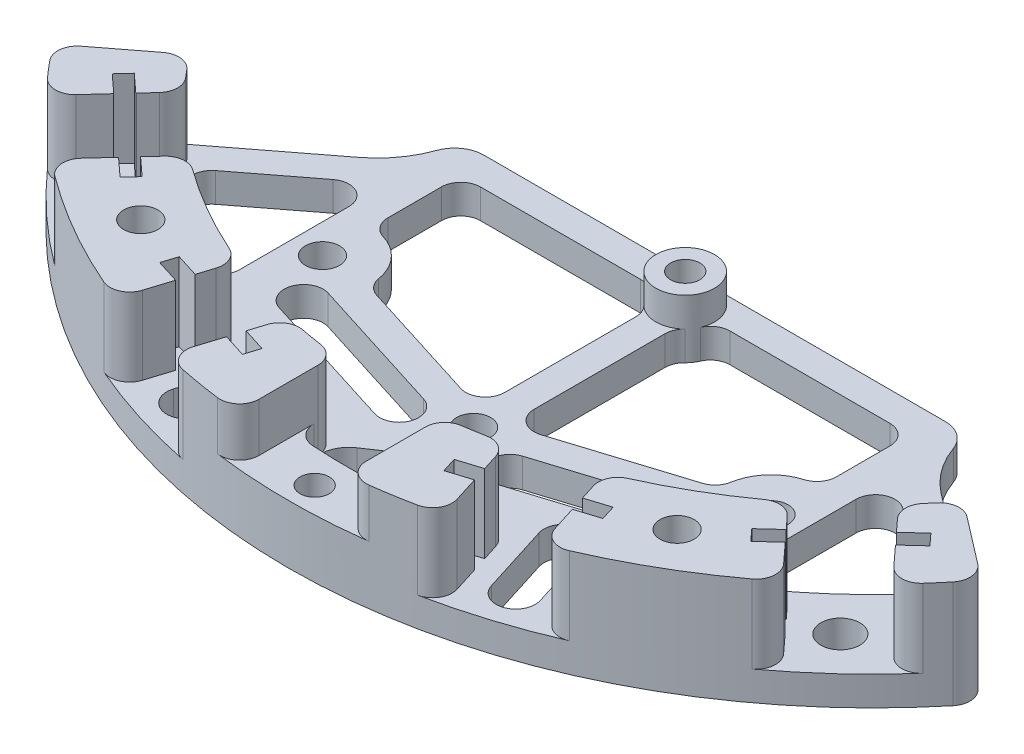
SolidWorks part; units mm, degrees
note: '?' marks a value the reader was unsure of.
ref_plane "Front Plane" through (0, 0, 0) normal (0, 0, 1) x (1, 0, 0)
ref_plane "Top Plane" through (0, 0, 0) normal (0, 1, 0) x (1, 0, 0)
ref_plane "Right Plane" through (0, 0, 0) normal (1, 0, 0) x (0, 0, -1)
sketch "Sketch1" plane through (0, 0, 0) normal (0, 1, 0) x (1, 0, 0)
  line L0 (-26, -16.3) -> (26, -16.3)
  line L3 (0, 0) -> (0, -80774.1077) construction
  line L5 (-47.6012, -36.5257) -> (-26, -19.9505)
  line L6 (-26, -19.9505) -> (-26, -16.3)
  line L7 (47.6012, -36.5257) -> (26, -19.9505)
  line L8 (26, -19.9505) -> (26, -16.3)
  arc A0 (-47.6012, -36.5257) -> (47.6012, -36.5257) centre (0, 0) ccw
  dimension "D1" = 60
  dimension "D2" = 105
  dimension "D4" = 52
  dimension "D5" = 16.3
extrude "Boss-Extrude1" add sketch "Sketch1" along normal blind 3
sketch "Sketch2" plane through (0, 3, 0) normal (0, 1, 0) x (1, 0, 0)
  line L0 (26, -16.3) -> (-26, -16.3) construction
  line L1 (0, 0) -> (0, -50000) construction
  circle A0 centre (-23, -33.5) radius 1.75
  circle A1 centre (23, -33.5) radius 1.75
  dimension "D1" = 3.5
  dimension "D2" = 17.2
  dimension "D3" = 46
extrude "Cut-Extrude1" cut sketch "Sketch2" against normal through all
sketch "Sketch3" plane through (0, 3, 0) normal (0, 1, 0) x (1, 0, 0)
  line L0 (-47.6012, -36.5257) -> (-39.6677, -30.4381)
  line L1 (-43.3943, -41.4359) -> (-40.0825, -37.8217)
  line L2 (-32.238, -50.6035) -> (-26.865, -42.1696)
  line L3 (-40.0825, -37.8217) -> (-41.9257, -36.1327)
  line L4 (-41.9257, -36.1327) -> (-40.8448, -34.953)
  line L5 (-40.8448, -34.953) -> (-39.0016, -36.642)
  line L6 (-39.0016, -36.642) -> (-36.6204, -34.0434)
  line L7 (-30.7221, -39.4481) -> (-33.1034, -42.0467)
  line L8 (-33.1034, -42.0467) -> (-31.2602, -43.7357)
  line L9 (-31.2602, -43.7357) -> (-32.3411, -44.9154)
  line L10 (-32.3411, -44.9154) -> (-34.1843, -43.2264)
  line L11 (-34.1843, -43.2264) -> (-37.4961, -46.8406)
  line L12 (-3.1979, -3.4899) -> (-31694.9476, -34588.9658) construction
  line L13 (-11.1484, -63.2498) -> (-34596.7728, 31628.636) construction
  line L14 (0, -2.3226) -> (0, -50002.3226) construction
  line L15 (-26, -19.9505) -> (-47.6012, -36.5257) construction
  arc A0 (-47.6012, -36.5257) -> (-43.3943, -41.4359) centre (0, 0) ccw
  arc A1 (-47.6012, -36.5257) -> (47.6012, -36.5257) centre (0, 0) ccw construction
  arc A2 (-39.6677, -30.4381) -> (-36.6204, -34.0434) centre (0, 0) ccw
  arc A3 (-30.7221, -39.4481) -> (-26.865, -42.1696) centre (0, 0) ccw
  arc A4 (-37.4961, -46.8406) -> (-32.238, -50.6035) centre (0, 0) ccw
  point P26 (-29.5515, -46.3865)
  point P27 (-43.6344, -33.4819)
  dimension "D1" = 20
  dimension "D2" = 10
  dimension "D3" = 1.6
  dimension "D4" = 13
  dimension "D5" = 8
extrude "Boss-Extrude2" add sketch "Sketch3" along normal blind 8
ref_axis "Axis1" through (0, -0.65, 0) along (0, 1, 0)?
pattern_circular "CirPattern1" count 2 every 25 about axis through (0, 0, 0) along (0, 1, 0) of "Boss-Extrude2"
sketch "Sketch5" plane through (0, 3, 0) normal (0, 1, 0) x (1, 0, 0)
  line L0 (-23.0874, -44.3505) -> (-27.7049, -53.2206) construction
  line L1 (-32.238, -50.6035) -> (-26.865, -42.1696)
  line L2 (-23.0874, -44.3505) -> (-27.7049, -53.2206)
  arc A0 (-26.865, -42.1696) -> (-23.0874, -44.3505) centre (0, 0) ccw
  arc A1 (-32.238, -50.6035) -> (-27.7049, -53.2206) centre (0, 0) ccw
extrude "Boss-Extrude3" add sketch "Sketch5" along normal up to surface (8 mm away) up to face at (-32.2866, 11, 44.1378)
sketch "Sketch19" plane through (0, 11, 0) normal (0, 1, 0) x (1, 0, 0)
  line L0 (0, 0) -> (-25000, -43301.2702) construction
  line L1 (-30.7221, -39.4481) -> (-33.1034, -42.0467) construction
  line L2 (-19.8619, -49.6917) -> (-18.802, -46.3302) construction
  circle A0 centre (-27.5, -47.6314) radius 1.75
  dimension "D1" = 3.5
  dimension "D2" = 55
extrude "Cut-Extrude11" cut sketch "Sketch19" against normal through all
mirror "Mirror1" about plane through (0, 0, 0) normal (1, 0, 0) of "Cut-Extrude11", "CirPattern1", "Boss-Extrude2", "Boss-Extrude3"
fillet "Fillet2" radius 10 2 edges at (26, 1.5, 19.9505) (-26, 1.5, 19.9505)
sketch "Sketch6" plane through (0, 3, 0) normal (0, 1, 0) x (1, 0, 0)
  line L1 (-7.0484, -53.538) -> (-7.8316, -59.4867)
  line L2 (7.0484, -53.538) -> (7.8316, -59.4867)
  line L3 (0, -1.1899) -> (0, -50001.1899) construction
  line L4 (26, -16.3) -> (-26, -16.3) construction
  arc A0 (-7.0484, -53.538) -> (7.0484, -53.538) centre (0, 0) ccw
  arc A1 (-7.8316, -59.4867) -> (7.8316, -59.4867) centre (0, 0) ccw
  arc A2 (-7.8316, -59.4867) -> (7.8316, -59.4867) centre (0, 0) ccw construction
  circle A3 centre (0, -19.3) radius 3
  dimension "D1" = 6
  dimension "D2" = 6
extrude "Boss-Extrude4" add sketch "Sketch6" along normal blind 3
sketch "Sketch12" plane through (0, 3, 0) normal (0, 1, 0) x (1, 0, 0)
  line L0 (0, 0) -> (0, -50000) construction
  line L1 (-5.5, -49.6966) -> (-5.5, -59.7474)
  line L2 (-7.8316, -59.4867) -> (-6.5263, -49.5722)
  arc A0 (-6.5263, -49.5722) -> (-5.5, -49.6966) centre (0, 0) ccw
  arc A1 (-7.8316, -59.4867) -> (-5.5, -59.7474) centre (0, 0) ccw
  dimension "D1" = 5.5
extrude "Boss-Extrude5" add sketch "Sketch12" along normal up to surface (8 mm away)
mirror "Mirror5" about plane through (0, 0, 0) normal (1, 0, 0) of "Boss-Extrude5"
sketch "Sketch7" plane through (0, 6, 0) normal (0, 1, 0) x (1, 0, 0)
  line L0 (0, 0) -> (0, -50000) construction
  circle A0 centre (0, -19.3) radius 1.5
  circle A1 centre (0, -57.3) radius 1.5
  dimension "D2" = 3
  dimension "D1" = 38
extrude "Cut-Extrude2" cut sketch "Sketch7" against normal through all
ref_plane "Plane1" through (0, 0, 0) normal (0.7373, 0, 0.6756) x (0.6756, 0, -0.7373)
ref_plane "Plane2" through (0, 0, 0) normal (-0.9537, 0, -0.3007) x (-0.3007, 0, 0.9537)
ref_plane "Plane3" through (0, 0, 0) normal (-0.9537, 0, 0.3007) x (0.3007, 0, 0.9537)
ref_plane "Plane4" through (0, 0, 0) normal (0.7373, 0, -0.6756) x (-0.6756, 0, -0.7373)
sketch "Sketch10" plane through (0, 0, 0) normal (0, -1, 0) x (1, 0, 0)
  line L0 (19.9851, 38.4432) -> (5.6793, 42.9538) construction
  line L1 (19.3837, 36.5358) -> (5.0779, 41.0464)
  line L2 (20.5865, 40.3507) -> (6.2807, 44.8613)
  line L3 (0, 0) -> (15035.29, 47685.8475) construction
  line L4 (17.8908, 35.958) -> (23.9049, 55.0323) construction
  line L5 (11.9835, 58.7911) -> (5.9693, 39.7168) construction
  line L6 (0, 0) -> (0, 50000) construction
  line L7 (5.9693, 39.7168) -> (17.8908, 35.958) construction
  arc A0 (19.3837, 36.5358) -> (20.5865, 40.3507) centre (19.9851, 38.4432) ccw
  arc A1 (6.2807, 44.8613) -> (5.0779, 41.0464) centre (5.6793, 42.9538) ccw
  point P3 (12.8322, 40.6985)
  dimension "D1" = 15
  dimension "D2" = 2
  dimension "D3" = 3
extrude "Cut-Extrude3" cut sketch "Sketch10" against normal up to next
mirror "Mirror2" about plane through (0, 0, 0) normal (1, 0, 0) of "Cut-Extrude3"
sketch "Sketch11" plane through (0, 3, 0) normal (0, 1, 0) x (1, 0, 0)
  line L0 (-23, -19.3) -> (-3, -19.3)
  line L1 (-1.5, -21.8981) -> (-1.5, -39.0289)
  line L2 (-1.5, -39.0289) -> (-18.0105, -33.8232)
  line L3 (-23, -19.3) -> (-23, -28.5)
  line L4 (-5.0779, -41.0464) -> (-19.3837, -36.5358) construction
  line L5 (0, 0) -> (0, -50000) construction
  line L6 (0, -16.3) -> (-26, -16.3) construction
  line L7 (-26, -23.7319) -> (-26, -42.7083)
  line L8 (-26, -23.7319) -> (-37.7699, -32.7633)
  line L9 (-29.8207, -22.8822) -> (-39.6677, -30.4381) construction
  line L10 (-0.5806, -0.6337) -> (-33780.091, -36864.5005) construction
  line L11 (0, 0) -> (-15035.29, -47685.8475) construction
  line L12 (-39.0016, -36.642) -> (-36.6204, -34.0434) construction
  line L13 (-30.7221, -39.4481) -> (-33.1034, -42.0467) construction
  line L14 (-19.8619, -49.6917) -> (-18.802, -46.3302) construction
  line L15 (-11.1722, -48.7358) -> (-12.2321, -52.0974) construction
  line L16 (-16.8917, -53.5737) -> (-14.6364, -46.4208) construction
  line L17 (-18.7992, -52.9723) -> (-16.5439, -45.8194)
  line L18 (-14.9843, -54.1751) -> (-12.729, -47.0222)
  line L19 (-20.5865, -40.3507) -> (-6.2807, -44.8613) construction
  arc A0 (-18.0105, -33.8232) -> (-23, -28.5) centre (-23, -33.5) ccw
  arc A1 (-3, -19.3) -> (-1.5, -21.8981) centre (0, -19.3) ccw
  arc A2 (-37.7699, -32.7633) -> (-26, -42.7083) centre (0, 0) ccw
  arc A3 (-39.6677, -30.4381) -> (-36.6204, -34.0434) centre (0, 0) ccw construction
  circle A4 centre (0, -19.3) radius 3 construction
  circle A5 centre (-37.1575, -40.5503) radius 2
  arc A6 (-18.7992, -52.9723) -> (-14.9843, -54.1751) centre (-16.8917, -53.5737) ccw
  arc A7 (-12.729, -47.0222) -> (-16.5439, -45.8194) centre (-14.6364, -46.4208) ccw
  point P44 (-15.7641, -49.9973)
  dimension "D5" = 5
  dimension "D6" = 3
  dimension "D8" = 4
  dimension "D1" = 3
  dimension "D2" = 3
  dimension "D3" = 3
  dimension "D4" = 23
  dimension "D7" = 3
  dimension "D9" = 4
  dimension "D10" = 7.5
  dimension "D11" = 55
extrude "Cut-Extrude4" cut sketch "Sketch11" against normal through all
fillet "Fillet3" radius 2 9 edges at (-1.5, 1.5, 39.0289) (-1.5, 1.5, 21.8981) (-3, 1.5, 19.3) (-18.0105, 1.5, 33.8232) (-23, 1.5, 28.5) (-23, 1.5, 19.3) (-37.7699, 1.5, 32.7633) (-26, 1.5, 42.7083) (-26, 1.5, 23.7319)
mirror "Mirror3" about plane through (0, 0, 0) normal (1, 0, 0) of "Fillet3", "Cut-Extrude4"
sketch "Sketch17" plane through (0, 3, 0) normal (0, 1, 0) x (1, 0, 0)
  line L0 (5.5, -53.7192) -> (5.5, -49.6966)
  line L1 (5.5, -49.6966) -> (0, -46)
  line L2 (0, -46) -> (-5.5, -49.6966)
  line L3 (-5.5, -49.6966) -> (-5.5, -53.7192)
  line L4 (0, 0) -> (0, -50000) construction
  arc A0 (-5.5, -53.7192) -> (5.5, -53.7192) centre (0, 0) ccw
  dimension "D1" = 46
extrude "Cut-Extrude10" cut sketch "Sketch17" against normal through all
fillet "Fillet1" radius 2 29 edges at (-47.6012, 5.5, 36.5257) (47.6012, 5.5, 36.5257) (43.3943, 7, 41.4359) (39.6677, 7, 30.4381) (36.6204, 7, 34.0434) (37.4961, 7, 46.8406) (30.7221, 7, 39.4481) (21.8171, 7, 55.8929) (18.802, 7, 46.3302) (14.1873, 7, 58.2985) (11.1722, 7, 48.7358) (-5.5, 3, 53.7192) (-5.5, 8.5, 59.7474) (-5.5, 7, 49.6966) (5.5, 7, 49.6966) (-36.6204, 7, 34.0434) (5.5, 8.5, 59.7474) (5.5, 3, 53.7192) (-37.4961, 7, 46.8406) (-30.7221, 7, 39.4481) (0, 1.5, 46) (-21.8171, 7, 55.8929) (-18.802, 7, 46.3302) (-14.1873, 7, 58.2985) (-11.1722, 7, 48.7358)
sketch "Sketch16" plane through (0, 3, 0) normal (0, 1, 0) x (1, 0, 0)
  line L0 (0, 0) -> (0, -50000) construction
  circle A1 centre (0, -41) radius 1.75
  dimension "D3" = 3.5
  dimension "D4" = 41
extrude "Cut-Extrude9" cut sketch "Sketch16" against normal through all
fillet "Fillet4" radius 3 4 edges at (26, 1.5, 16.3) (-26, 1.5, 16.3) (5.5, 1.5, 49.6966) (-5.5, 1.5, 49.6966)
